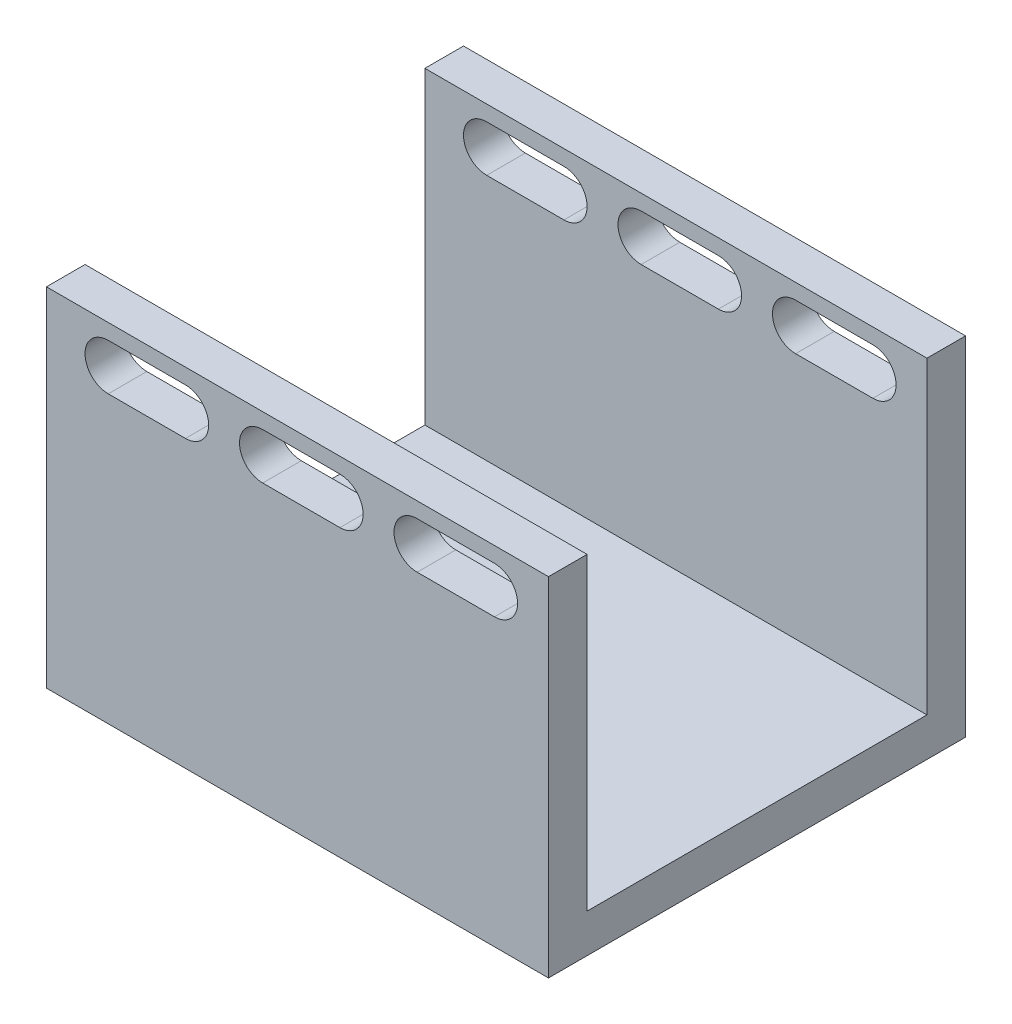
SolidWorks part; units mm, degrees
ref_plane "Front Plane" through (0, 0, 0) normal (0, 0, 1) x (1, 0, 0)
ref_plane "Top Plane" through (0, 0, 0) normal (0, 1, 0) x (1, 0, 0)
ref_plane "Right Plane" through (0, 0, 0) normal (1, 0, 0) x (0, 0, -1)
sketch "Sketch1" plane through (0, 0, 0) normal (0, 1, 0) x (1, 0, 0)
  line L1 (32.5, 22) -> (-32.5, 22)
  line L2 (32.5, 22) -> (32.5, -22)
  line L3 (32.5, -22) -> (-32.5, -22)
  line L4 (-32.5, 22) -> (-32.5, -22)
  line L5 (0, -22) -> (0, 22) construction
  line L6 (32.5, 0) -> (-32.5, 0) construction
  point P0 (0, 0)
  dimension "D1" = 65
  dimension "D2" = 44
extrude "Boss-Extrude1" add sketch "Sketch1" along normal blind 5
sketch "Sketch2" plane through (0, 0, 0) normal (0, 1, 0) x (1, 0, 0)
  line L0 (-32.5, -22) -> (32.5, -22) construction
  line L1 (32.5, 22) -> (-32.5, 22) construction
  line L2 (-32.5, -22) -> (32.5, -22)
  line L3 (32.5, 22) -> (-32.5, 22)
  line L4 (-32.5, 22) -> (-32.5, 27)
  line L5 (-32.5, 27) -> (32.5, 27)
  line L6 (32.5, 27) -> (32.5, 22)
  line L7 (32.5, -22) -> (32.5, -27)
  line L8 (32.5, -27) -> (-32.5, -27)
  line L9 (-32.5, -27) -> (-32.5, -22)
  dimension "D1" = 5
  dimension "D2" = 5
extrude "Boss-Extrude2" add sketch "Sketch2" along normal blind 45
sketch "Sketch3" plane through (0, 0, 27) normal (0, 0, 1) x (1, 0, 0)
  line L0 (-24.5, 40) -> (-14.5, 40) construction
  line L1 (-24.5, 43) -> (-14.5, 43)
  line L2 (-24.5, 37) -> (-14.5, 37)
  line L3 (-19.5, 40) -> (-19.5, 45) construction
  line L4 (-32.5, 45) -> (32.5, 45) construction
  line L5 (-27.5, 40) -> (-32.5, 40)
  line L6 (-32.5, 45) -> (-32.5, 0) construction
  line L7 (-4.5, 37) -> (5.5, 37)
  line L8 (-4.5, 43) -> (5.5, 43)
  line L9 (-4.5, 40) -> (5.5, 40) construction
  line L10 (15.5, 37) -> (25.5, 37)
  line L11 (15.5, 43) -> (25.5, 43)
  line L12 (15.5, 40) -> (25.5, 40) construction
  arc A0 (-24.5, 43) -> (-24.5, 37) centre (-24.5, 40) ccw
  arc A1 (-14.5, 37) -> (-14.5, 43) centre (-14.5, 40) ccw
  arc A2 (-4.5, 43) -> (-4.5, 37) centre (-4.5, 40) ccw
  arc A3 (5.5, 37) -> (5.5, 43) centre (5.5, 40) ccw
  arc A4 (15.5, 43) -> (15.5, 37) centre (15.5, 40) ccw
  arc A5 (25.5, 37) -> (25.5, 43) centre (25.5, 40) ccw
  point P2 (-19.5, 40)
  point P18 (0.5, 40)
  point P25 (20.5, 40)
  dimension "D4" = 3
  dimension "D1" = 5
  dimension "D2" = 10
  dimension "D3" = 5
extrude "Cut-Extrude1" cut sketch "Sketch3" against normal through all contours L7 A3 L8 A2 | L2 A1 L1 A0 | L10 A5 L11 A4 region at (-19.5, 40, 27) region at (0.5, 40, 27) region at (20.5, 40, 27)
